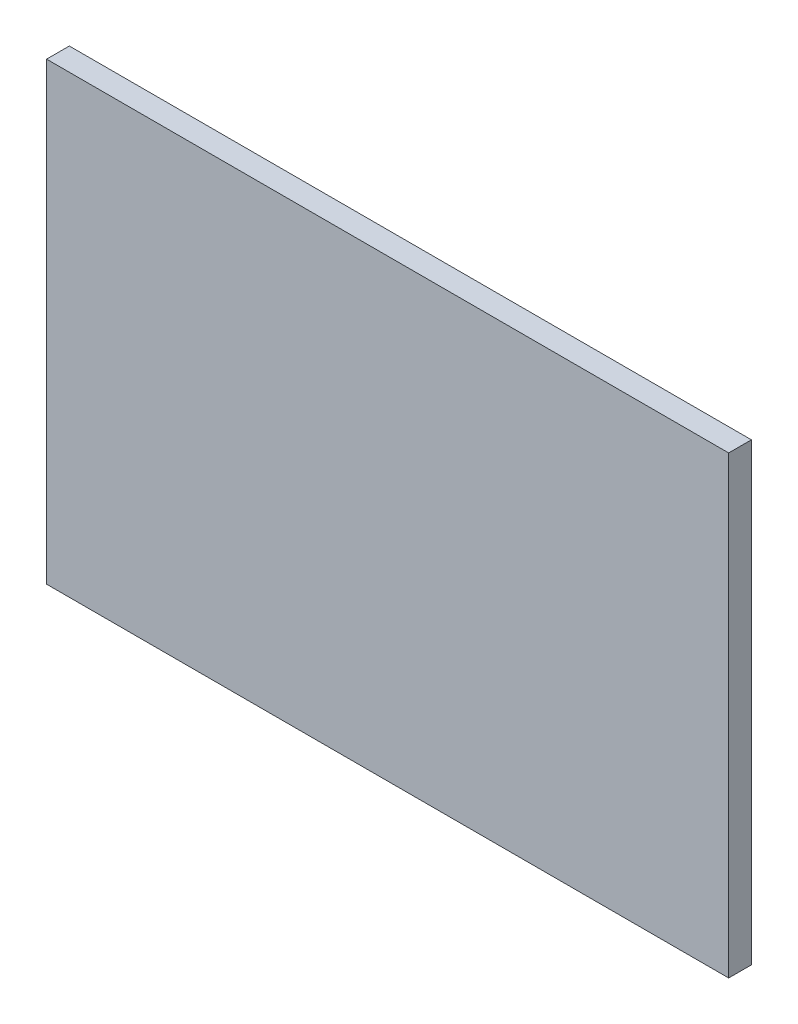
SolidWorks part; units mm, degrees
ref_plane "Alzado" through (0, 0, 0) normal (0, 0, 1) x (1, 0, 0)
ref_plane "Planta" through (0, 0, 0) normal (0, 1, 0) x (1, 0, 0)
ref_plane "Vista lateral" through (0, 0, 0) normal (1, 0, 0) x (0, 0, -1)
sketch "Croquis1" plane through (0, 0, 0) normal (0, 0, 1) x (1, 0, 0)
  line L1 (-294.9346, 8.7369) -> (5.0654, 8.7369)
  line L2 (-294.9346, 8.7369) -> (-294.9346, -191.2631)
  line L3 (-294.9346, -191.2631) -> (5.0654, -191.2631)
  line L4 (5.0654, 8.7369) -> (5.0654, -191.2631)
  line L5 (-294.9346, 8.7369) -> (5.0654, -191.2631) construction
  line L6 (-294.9346, -191.2631) -> (5.0654, 8.7369) construction
  point P0 (-144.9346, -91.2631)
  dimension "D1" = 300
  dimension "D2" = 200
extrude "Saliente-Extruir1" add sketch "Croquis1" along normal blind 10
